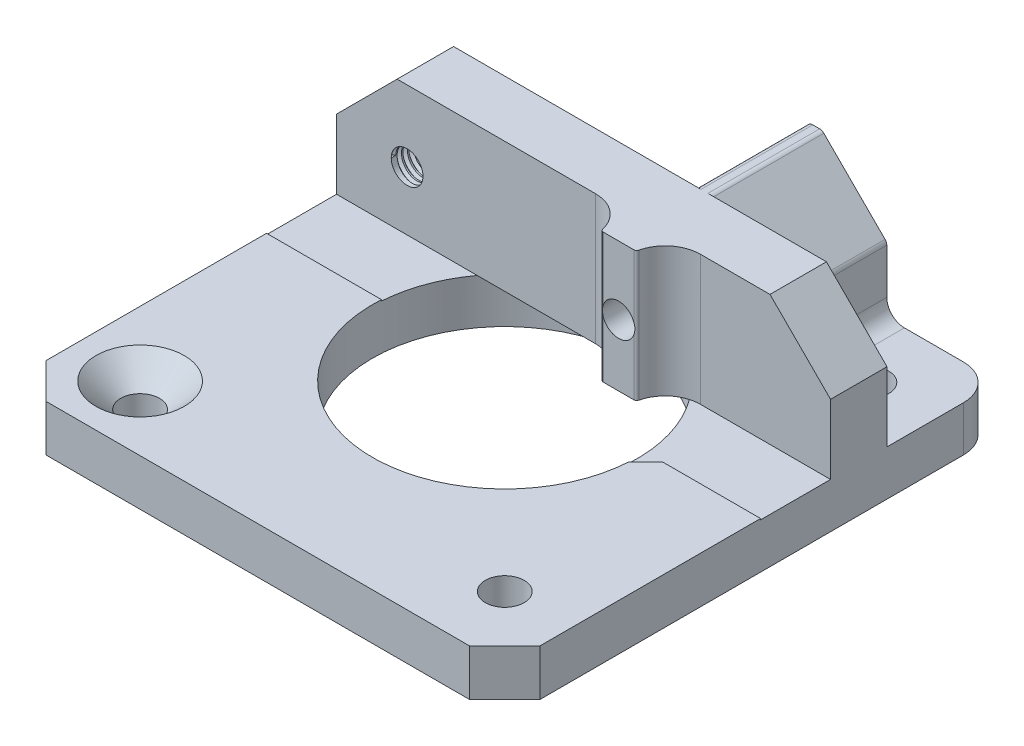
SolidWorks part; units mm, degrees
ref_plane "Front Plane" through (0, 0, 0) normal (0, 0, 1) x (1, 0, 0)
ref_plane "Top Plane" through (0, 0, 0) normal (0, 1, 0) x (1, 0, 0)
ref_plane "Right Plane" through (0, 0, 0) normal (1, 0, 0) x (0, 0, -1)
sketch "Sketch1" plane through (0, 0, 0) normal (0, 1, 0) x (1, 0, 0)
  line L0 (-15.5, 15.5) -> (15.5, 15.5) construction
  line L1 (-21, -21) -> (21, -21)
  line L2 (-21, -21) -> (-21, 21)
  line L3 (-21, 21) -> (21, 21)
  line L4 (21, -21) -> (21, 21)
  line L5 (-21, -21) -> (21, 21) construction
  line L6 (-21, 21) -> (21, -21) construction
  line L7 (-15.5, 15.5) -> (-15.5, -15.5) construction
  circle A0 centre (-15.5, 15.5) radius 1.65
  circle A1 centre (15.5, 15.5) radius 1.65
  circle A2 centre (15.5, -15.5) radius 1.65
  circle A3 centre (-15.5, -15.5) radius 1.65
  circle A4 centre (0, 0) radius 11.25
  point P0 (0, 0)
  dimension "D3" = 5.5
  dimension "D4" = 3.3
  dimension "D9" = 5.5
  dimension "D10" = 22.5
  dimension "D1" = 42
  dimension "D2" = 42
  dimension "D7" = 31
  dimension "D8" = 31
  dimension "D5" = 2
  dimension "D6" = 2
extrude "Boss-Extrude1" add sketch "Sketch1" along normal blind 3.85
fillet "Fillet1" radius 3 2 edges at (21, 1.925, -21) (-21, 1.925, -21)
chamfer "Chamfer1" distance 3 angle 45 2 edges at (-21, 1.925, 21) (21, 1.925, 21)
sketch "Sketch2" plane through (0, 3.85, 0) normal (0, 1, 0) x (1, 0, 0)
  line L0 (-21, 18) -> (-21, -18) construction
  line L1 (-21, 11.5) -> (21, 11.5)
  line L2 (-21, 11.5) -> (-21, 6.7)
  line L3 (-21, 6.7) -> (21, 6.7)
  line L4 (21, 11.5) -> (21, 6.7)
  line L5 (21, -18) -> (21, 18) construction
  line L6 (18, 21) -> (-18, 21) construction
  line L12 (-0.52, 21) -> (11.48, 21)
  line L13 (-0.52, 21) -> (-0.52, 11.5)
  line L14 (-0.52, 11.5) -> (11.48, 11.5)
  line L15 (11.48, 21) -> (11.48, 11.5)
  line L16 (3.98, 6.7) -> (6.98, 6.7)
  line L17 (3.98, 6.7) -> (3.98, 4.2)
  line L18 (3.98, 4.2) -> (6.98, 4.2)
  line L19 (6.98, 6.7) -> (6.98, 4.2)
  line M13 (-21, 18) -> (-21, -18)
  line M17 (21, -18) -> (21, 18)
  line M19 (18, 21) -> (-18, 21)
  circle M22 centre (0, 0) radius 11.25
  dimension "D1" = 4.8
  dimension "D2" = 9.5
  dimension "D3" = 9.52
  dimension "D4" = 12
  dimension "D5" = 3
  dimension "D6" = 2.5
  dimension "D7" = 14.02
extrude "Boss-Extrude2" add sketch "Sketch2" along normal blind 11.05 contours L15 L13 L1 M19 | L3 M22 | L19 L3 L17 L18 | L3 L1 M13 M22 M17 region at (-10.76, 3.85, -11.0773) region at (5.48, 3.85, -16.25) region at (0, 3.85, -8.5558) region at (5.48, 3.85, -5.45)
fillet "Fillet2" radius 5 1 edges at (-0.52, 3.85, -16.25)
fillet "Fillet3" radius 1.5 1 edges at (11.48, 3.85, -16.25)
chamfer "Chamfer4" distance 5.5 angle 45 2 edges at (11.48, 14.9, -16.25) (-0.52, 14.9, -16.25)
fillet "Fillet5" radius 0.5 4 edges at (11.48, 9.4, -16.25) (5.98, 14.9, -16.25) (4.98, 14.9, -16.25) (-0.52, 9.4, -16.25)
chamfer "Chamfer3" distance 5.15 angle 45 2 edges at (21, 14.9, -9.1) (-21, 14.9, -9.1)
sketch "Sketch3" plane through (0, 0, -4.2) normal (0, 0, 1) x (1, 0, 0)
  line L0 (5.48, 14.9) -> (5.48, 3.85) construction
  line L1 (3.98, 14.9) -> (6.98, 14.9) construction
  line L2 (3.98, 3.85) -> (6.98, 3.85) construction
  circle A0 centre (5.48, 9.1) radius 1.375
  dimension "D1" = 2.75
  dimension "D2" = 5.8
extrude "Cut-Extrude1" cut sketch "Sketch3" against normal up to next
fillet "Fillet6" radius 3 2 edges at (6.98, 9.375, -6.7) (3.98, 9.375, -6.7)
fillet "Fillet7" radius 0.25 2 edges at (6.98, 9.375, -4.2) (3.98, 9.375, -4.2)
sketch "Sketch4" plane through (0, 0, -21) normal (0, 0, -1) x (-1, 0, 0)
  circle A0 centre (-5.48, 9.1) radius 2.5
  dimension "D1" = 5
extrude "Cut-Extrude2" cut sketch "Sketch4" against normal blind 6.5
thread "Thread1" pitch 0.8 method cut profile "Thread Profile1" start angle 0, offset 0, length 6.5, pitch 1, diameter 5
ref_plane "Plane1" through (7.98, 9.1, -21) normal (0, -1, 0) x (1, 0, 0)
sketch "Thread Profile1" plane through (7.98, 9.1, -21) normal (0, -1, 0) x (1, 0, 0)
  line L0 (0, 0) -> (0, 0.8) construction
  line L1 (0, 0) -> (0.433, 0.25)
  line L2 (0.433, 0.25) -> (0.433, 0.35)
  line L3 (0.433, 0.35) -> (0, 0.6)
  line L4 (0.433, 0.3) -> (0, 0.3) construction
  line L11 (0, 0) -> (0, 0.6)
  point P2 (0, 0)
  dimension "Pitch" = 0.8
  dimension "Profile_Angle" = 60
  dimension "Profile_Land" = 0.1
  dimension "Profile_Height" = 0.433
fillet "Fillet8" radius 0.2 1 edges at (2.98, 9.1, -21)
sketch "Sketch8" plane through (0, 3.85, 0) normal (0, 1, 0) x (1, 0, 0)
  line L0 (-21, -18) -> (-21, 0.75)
  line L1 (-21, 6.7) -> (-21, -18) construction
  line L2 (-18, -21) -> (18, -21) construction
  line L5 (-21, -18) -> (-18, -21)
  line L6 (-18, -21) -> (18, -21)
  line L7 (18, -21) -> (21, -18)
  line L8 (21, -18) -> (21, 0.75)
  line L10 (21, -18) -> (21, 6.7) construction
  line L12 (-21, 0.75) -> (-11.225, 0.75)
  line L13 (21, 0.75) -> (12.6446, 0.75)
  line L14 (12.6446, 0.75) -> (11.2304, -0.6642)
  circle A2 centre (-15.5, -15.5) radius 1.65
  circle A3 centre (15.5, -15.5) radius 1.65
  arc A4 (-9.0373, 6.7) -> (9.1204, 6.5864) centre (0, 0) ccw construction
  arc A5 (11.2304, -0.6642) -> (-11.225, 0.75) centre (0, 0) cw
  dimension "D5" = 11.25
  dimension "D6" = 3.3
  dimension "D7" = 3.3
  dimension "D1" = 21.75
  dimension "D2" = 2
  dimension "D3" = 45
  dimension "D4" = 21.75
extrude "Boss-Extrude3" add sketch "Sketch8" along normal blind 0.1
sketch "Sketch9" plane through (0, 0, -6.7) normal (0, 0, 1) x (1, 0, 0)
  line L0 (-21, 9.75) -> (-21, 3.85) construction
  line L1 (-21, 3.85) -> (-9.0373, 3.85) construction
  circle A0 centre (-15, 8.85) radius 1.35
  dimension "D1" = 2.7
  dimension "D2" = 6
  dimension "D3" = 5
extrude "Cut-Extrude3" cut sketch "Sketch9" against normal up to next
thread "Thread2" pitch 0.5 method cut profile "Thread Profile2" start angle 0, offset 0, length 0, pitch 0.5, diameter 2.7
ref_plane "Plane2" through (-16.35, 8.85, -6.7) normal (0, -1, 0) x (-1, 0, 0)
sketch "Thread Profile2" plane through (-16.35, 8.85, -6.7) normal (0, -1, 0) x (-1, 0, 0)
  line L0 (0, 0) -> (0, 0.5) construction
  line L1 (0, 0) -> (0.2706, 0.1562)
  line L2 (0.2706, 0.1562) -> (0.2706, 0.2187)
  line L3 (0.2706, 0.2187) -> (0, 0.375)
  line L4 (0.2706, 0.1875) -> (0, 0.1875) construction
  line L11 (0, 0) -> (0, 0.375)
  point P2 (0, 0)
  dimension "Pitch" = 0.5
  dimension "Profile_Angle" = 60
  dimension "Profile_Land" = 0.0625
  dimension "Profile_Height" = 0.2706
chamfer "Chamfer5" distance 2.1 angle 45 1 edges at (-15.5, 3.95, 17.15)
